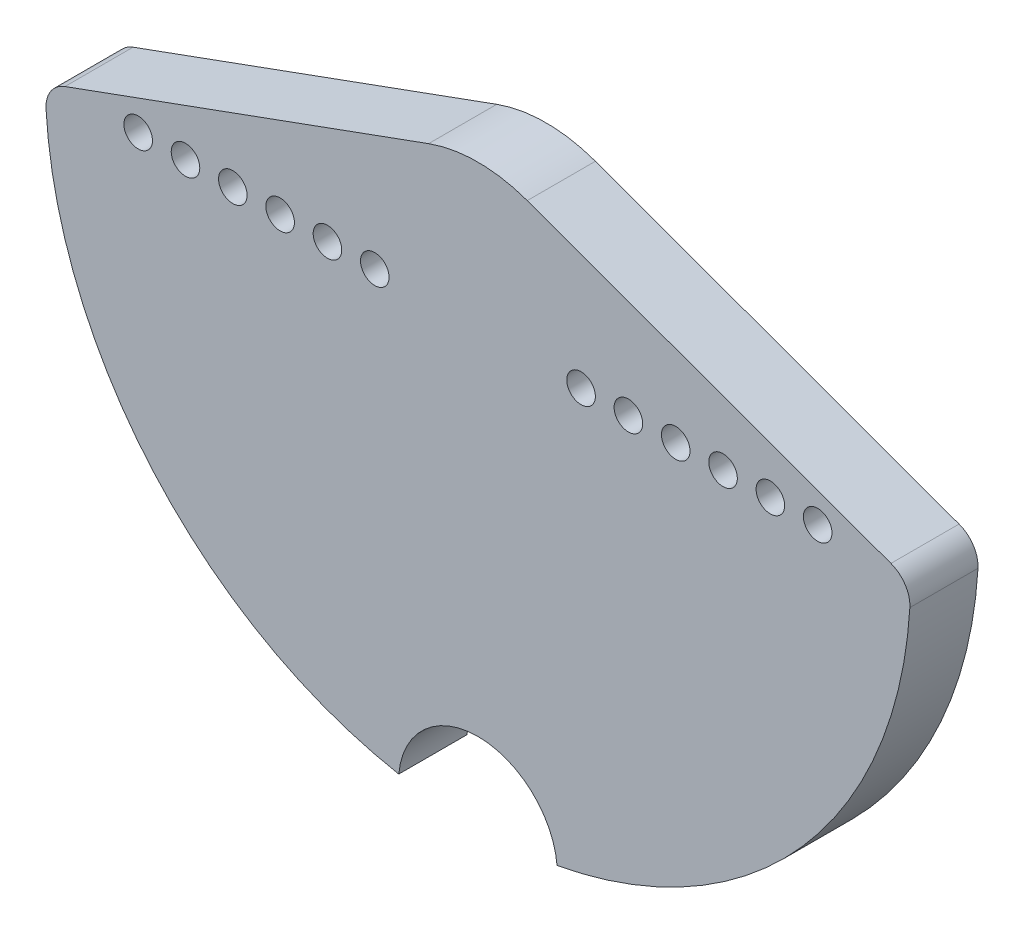
SolidWorks part; units mm, degrees
ref_plane "Front Plane" through (0, 0, 0) normal (0, 0, 1) x (1, 0, 0)
ref_plane "Top Plane" through (0, 0, 0) normal (0, 1, 0) x (1, 0, 0)
ref_plane "Right Plane" through (0, 0, 0) normal (1, 0, 0) x (0, 0, -1)
sketch "Sketch1" plane through (0, 0, 0) normal (0, 0, 1) x (1, 0, 0)
  line L0 (2.1718, 5.967) -> (18.1831, 0.1394)
  line L1 (0, 0) -> (0, -19.05) construction
  line L2 (-3.4852, -18.7285) -> (0, -19.05) construction
  line L3 (-2.1718, 5.967) -> (-18.1831, 0.1394)
  arc A1 (-19.0165, -1.1293) -> (-3.4852, -18.7285) centre (0, 0) ccw
  arc A2 (-3.4852, -18.7285) -> (3.4852, -18.7285) centre (0, -19.05) cw
  arc A3 (-18.1831, 0.1394) -> (-19.0165, -1.1293) centre (-17.7487, -1.054) ccw
  arc A4 (-2.1718, 5.967) -> (2.1718, 5.967) centre (0, 0) cw
  arc A5 (19.0165, -1.1293) -> (3.4852, -18.7285) centre (0, 0) cw
  arc A6 (18.1831, 0.1394) -> (19.0165, -1.1293) centre (17.7487, -1.054) cw
  point P7 (0, 0)
  dimension "D1" = 3.5
  dimension "D3" = 19.05
  dimension "D4" = 1.27
  dimension "D2" = 6.35
  dimension "D7" = 70
extrude "Boss-Extrude1" add sketch "Sketch1" along normal blind 3
sketch "Sketch2" plane through (0, 0, 3) normal (0, 0, 1) x (1, 0, 0)
  line L0 (0, -1.65) -> (0, 1.65) construction
  circle A0 centre (10.7917, 0) radius 0.375 construction
  circle A1 centre (-12.875, 0) radius 0.375
  circle A2 centre (8.7083, 0) radius 0.375 construction
  circle A3 centre (6.625, 0) radius 0.375 construction
  circle A6 centre (-12.875, 0) radius 0.375 construction
  circle A7 centre (-14.9583, 0) radius 0.375
  circle A8 centre (-14.9583, 0) radius 0.375 construction
  circle A9 centre (-4.5417, 0) radius 0.375
  circle A10 centre (-4.5417, 0) radius 0.375 construction
  circle A11 centre (-6.625, 0) radius 0.375
  circle A12 centre (-6.625, 0) radius 0.375 construction
  circle A13 centre (-8.7083, 0) radius 0.375
  circle A14 centre (-8.7083, 0) radius 0.375 construction
  circle A15 centre (-10.7917, 0) radius 0.375
  circle A16 centre (-10.7917, 0) radius 0.375 construction
  circle A17 centre (4.5417, 0) radius 0.375 construction
  circle A19 centre (14.9583, 0) radius 0.375 construction
  circle A20 centre (12.875, 0) radius 0.375 construction
  circle A21 centre (10.7917, 0) radius 0.121
  circle A22 centre (8.7083, 0) radius 0.121
  circle A23 centre (6.625, 0) radius 0.121
  circle A24 centre (-12.875, 0) radius 0.629
  circle A25 centre (-14.9583, 0) radius 0.629
  circle A26 centre (-4.5417, 0) radius 0.629
  circle A27 centre (-6.625, 0) radius 0.629
  circle A28 centre (-8.7083, 0) radius 0.629
  circle A29 centre (-10.7917, 0) radius 0.629
  circle A30 centre (4.5417, 0) radius 0.121
  circle A31 centre (14.9583, 0) radius 0.121
  circle A32 centre (12.875, 0) radius 0.121
  dimension "D1" = 0.254
  dimension "D2" = 0
  dimension "D3" = 0
  dimension "D4" = 0
  dimension "D5" = 0
  dimension "D6" = 0
  dimension "D7" = 0
extrude "Cut-Extrude1" cut sketch "Sketch2" against normal through all both and the other way through all
mirror "Mirror1" about plane through (0, 0, 0) normal (1, 0, 0) of "Cut-Extrude1"
